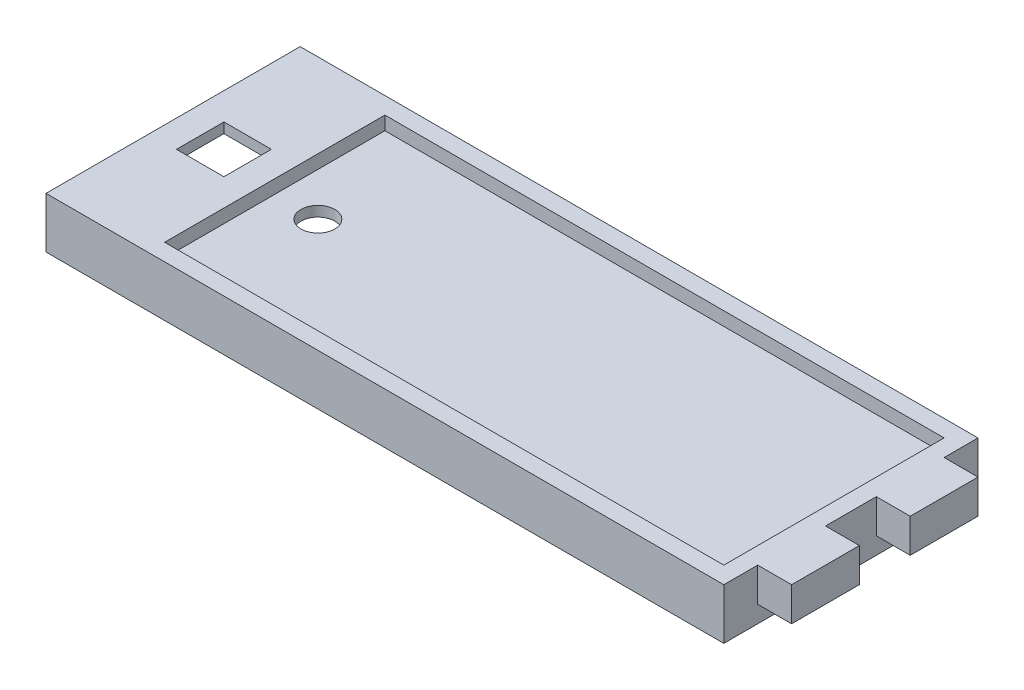
SolidWorks part; units mm, degrees
ref_plane "Front Plane" through (0, 0, 0) normal (0, 0, 1) x (1, 0, 0)
ref_plane "Top Plane" through (0, 0, 0) normal (0, 1, 0) x (1, 0, 0)
ref_plane "Right Plane" through (0, 0, 0) normal (1, 0, 0) x (0, 0, -1)
sketch "Sketch1" plane through (0, 0, 0) normal (0, 1, 0) x (1, 0, 0)
  line L1 (-60, 37.5) -> (140, 37.5)
  line L2 (-60, 37.5) -> (-60, -37.5)
  line L3 (-60, -37.5) -> (140, -37.5)
  line L4 (140, 37.5) -> (140, -37.5)
  point P0 (0, 0)
  dimension "D1" = 200
  dimension "D2" = 75
extrude "Boss-Extrude1" add sketch "Sketch1" along normal blind 15
sketch "Sketch9" plane through (0, 15, 0) normal (0, 1, 0) x (1, 0, 0)
  line L1 (-30, 32.5) -> (135, 32.5)
  line L2 (-30, 32.5) -> (-30, -32.5)
  line L3 (-30, -32.5) -> (135, -32.5)
  line L4 (135, 32.5) -> (135, -32.5)
  line L5 (140, -37.5) -> (140, 37.5) construction
  point P4 (135, 0)
  dimension "D1" = 165
  dimension "D2" = 65
  dimension "D3" = 0
  dimension "D4" = 5
extrude "Cut-Extrude5" cut sketch "Sketch9" against normal blind 4
shell "Shell3" thickness 3 removed face at (40, 0, 0) removed face at (-60, 7.5, 0)
sketch "Sketch14" plane through (140, 0, 0) normal (1, 0, 0) x (0, 0, -1)
  line L1 (-27.5, 15) -> (-7.5, 15)
  line L2 (-27.5, 15) -> (-27.5, 5)
  line L3 (-27.5, 5) -> (-7.5, 5)
  line L4 (-7.5, 15) -> (-7.5, 5)
  line L5 (7.5, 15) -> (27.5, 15)
  line L6 (7.5, 15) -> (7.5, 5)
  line L7 (7.5, 5) -> (27.5, 5)
  line L8 (27.5, 15) -> (27.5, 5)
  line L9 (-37.5, 15) -> (37.5, 15) construction
  line L10 (-37.5, 15) -> (-37.5, 0) construction
  line L11 (37.5, 15) -> (37.5, 0) construction
  point P12 (-37.5, 7.5)
  dimension "D1" = 20
  dimension "D2" = 10
  dimension "D3" = 10
  dimension "D4" = 10
extrude "Boss-Extrude5" add sketch "Sketch14" along normal blind 10
sketch "Sketch15" plane through (0, 11, 0) normal (0, 1, 0) x (1, 0, 0)
  circle A0 centre (-17.2823, 0) radius 5
extrude "Cut-Extrude7" cut sketch "Sketch15" against normal through all
sketch "Sketch16" plane through (0, 15, 0) normal (0, 1, 0) x (1, 0, 0)
  line L0 (-30, 32.5) -> (-30, -32.5) construction
  line L1 (-52, -7) -> (-38, -7)
  line L2 (-52, -7) -> (-52, 7)
  line L3 (-52, 7) -> (-38, 7)
  line L4 (-38, -7) -> (-38, 7)
  line L5 (-52, -7) -> (-38, 7) construction
  line L6 (-52, 7) -> (-38, -7) construction
  line L8 (140, 37.5) -> (-60, 37.5) construction
  point P0 (-45, 0)
  dimension "D1" = 14
  dimension "D2" = 14
  dimension "D3" = 8
  dimension "D4" = 30.5
extrude "Cut-Extrude8" cut sketch "Sketch16" against normal through all
